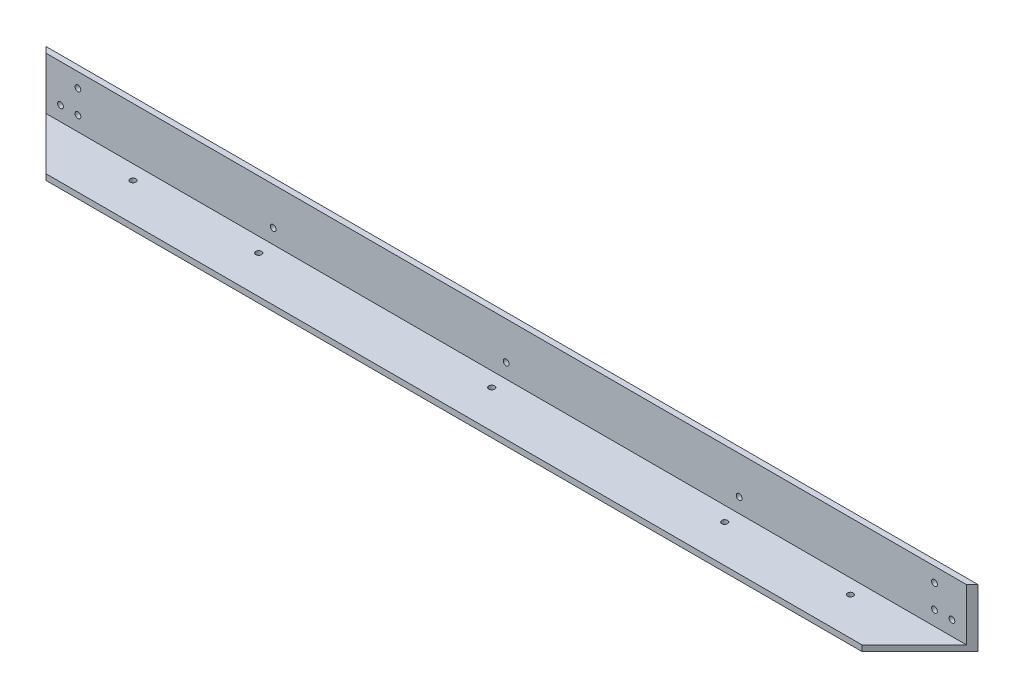
SolidWorks part; units mm, degrees
ref_plane "Front Plane" through (0, 0, 0) normal (0, 0, 1) x (1, 0, 0)
ref_plane "Top Plane" through (0, 0, 0) normal (0, 1, 0) x (1, 0, 0)
ref_plane "Right Plane" through (0, 0, 0) normal (1, 0, 0) x (0, 0, -1)
sketch "Sketch1" plane through (0, 0, 0) normal (1, 0, 0) x (0, 0, -1)
  line L0 (0, 0) -> (-31.75, 0)
  line L1 (-31.75, 0) -> (-31.75, 3.175)
  line L2 (-31.75, 3.175) -> (-3.175, 3.175)
  line L3 (-3.175, 3.175) -> (-3.175, 31.75)
  line L4 (-3.175, 31.75) -> (0, 31.75)
  line L5 (0, 31.75) -> (0, 0)
  dimension "LHeight" = 31.75
  dimension "LWidth" = 31.75
  dimension "LMaterialThickness" = 3.175
  dimension "D1" = 28.575
  dimension "D2" = 28.575
  dimension "D3" = 3.175
extrude "Boss-Extrude1" add sketch "Sketch1" along normal blind 510
chamfer "Chamfer6" distance 31.75 angle 45 1 edges at (510, 1.5875, 31.75)
chamfer "Chamfer7" distance 31.75 angle 45 1 edges at (0, 1.5875, 31.75)
sketch "TopHoles-Sketch3" plane through (0, 3.175, 0) normal (0, 1, 0) x (1, 0, 0)
  line L0 (510, 0) -> (0, 0) construction
  circle A9 centre (451.2625, -11.1125) radius 1.5875
  circle A10 centre (58.7375, -11.1125) radius 1.5875
  circle A13 centre (127.5, -11.1125) radius 1.5875
  circle A14 centre (255, -11.1125) radius 1.5875
  circle A15 centre (382.5, -11.1125) radius 1.5875
  point P8 (0, 0)
  point P9 (0, 0)
  point P10 (0, 0)
  point P11 (0, 0)
  point P12 (0, 0)
  point P13 (0, 0)
  point P14 (0, 0)
  dimension "D10" = 127.5
  dimension "D5" = 3.175
  dimension "D11" = 127.5
  dimension "D13" = 127.5
  dimension "D2" = 11.1125
  dimension "D3" = 58.7375
  dimension "D4" = 58.7375
extrude "TopHoles-Cut-Extrude2" cut sketch "TopHoles-Sketch3" against normal through all
sketch "FrontHoles-Sketch4" plane through (0, 0, 3.175) normal (0, 0, 1) x (1, 0, 0)
  line L0 (0, 0) -> (0, 31.75) construction
  line L1 (510, 0) -> (510, 31.75) construction
  line L3 (510, 31.75) -> (0, 31.75) construction
  line L7 (510, 0) -> (0, 0) construction
  circle A3 centre (489.3625, 23.8125) radius 1.5875
  circle A4 centre (20.6375, 23.8125) radius 1.5875
  circle A6 centre (11.1125, 11.1125) radius 1.5875
  circle A7 centre (20.6375, 11.1125) radius 1.5875
  circle A8 centre (489.3625, 11.1125) radius 1.5875
  circle A9 centre (498.8875, 11.1125) radius 1.5875
  circle A10 centre (127.5, 11.1125) radius 1.5875
  circle A11 centre (255, 11.1125) radius 1.5875
  circle A12 centre (382.5, 11.1125) radius 1.5875
  dimension "D2" = 3.175
  dimension "D7" = 11.1125
  dimension "D6" = 20.6375
  dimension "D5" = 20.6375
  dimension "D8" = 127.5
  dimension "D9" = 127.5
  dimension "D10" = 127.5
  dimension "D4" = 7.9375
  dimension "D11" = 11.1125
  dimension "D3" = 11.1125
extrude "FrontHoles-Cut-Extrude3" cut sketch "FrontHoles-Sketch4" against normal through all
equation "\"TopRailWidth\"= 1.25in"
equation "\"TopRailHeight\"= 1.25in"
equation "\"RailThickness\"= .125in'Spec"
equation "\"SideRailHoleY1FromEdge\"= \"HoleOffsetFromEdge\""
equation "\"SideRailHoleX1FromSide\"= \"HoleOffsetFromSide\""
equation "\"FrontBackRailLength\"= 510mm"
equation "\"VSWidth\"= 1.25in'Spec"
equation "\"HoleOffsetFromEdge\"= \"RailThickness\" * 2.5"
equation "\"HoleOffsetFromSide\"= \"RailThickness\" * 3.5"
equation "\"SideRailHoleX2FromSide\"= \"VSWidth\" - \"HoleOffsetFromEdge\" - \"RailThickness\"'Equals 20.6375"
equation "\"FasteningHoleDiameter\"= .125in"
equation "\"SideRailHoleY2FromSide\"= \"HoleOffsetFromSide\""
equation "\"LWidth@Sketch1\"=\"TopRailWidth\""
equation "\"LHeight@Sketch1\"=\"TopRailHeight\""
equation "\"LMaterialThickness@Sketch1\"=\"RailThickness\""
equation "\"D1@Boss-Extrude1\"= \"FrontBackRailLength\""
equation "\"D7@FrontHoles-Sketch4\"=\"SideRailHoleY2FromSide\""
equation "\"D1@Chamfer6\"=\"TopRailWidth\""
equation "\"D1@Chamfer7\"=\"TopRailWidth\""
equation "\"D6@FrontHoles-Sketch4\"=\"SideRailHoleX2FromSide\""
equation "\"TopHoleY1FromSide\"= \"HoleOffsetFromSide\""
equation "\"TopCBLength\"= \"TopRailWidth\" * 2'Equals 63.5"
equation "\"FrontOrBackEnclosureOffsets\"= \"FrontBackRailLength\" / 4"
equation "\"D10@TopHoles-Sketch3\"=\"FrontOrBackEnclosureOffsets\""
equation "\"D11@TopHoles-Sketch3\"=\"FrontOrBackEnclosureOffsets\""
equation "\"D13@TopHoles-Sketch3\"=\"FrontOrBackEnclosureOffsets\""
equation "\"D8@FrontHoles-Sketch4\"=\"FrontOrBackEnclosureOffsets\""
equation "\"D9@FrontHoles-Sketch4\"=\"FrontOrBackEnclosureOffsets\""
equation "\"D10@FrontHoles-Sketch4\"=\"FrontOrBackEnclosureOffsets\""
equation "\"D4@FrontHoles-Sketch4\"=\"SideRailHoleY1FromEdge\""
equation "\"D11@FrontHoles-Sketch4\"=\"SideRailHoleX1FromSide\""
equation "\"D2@FrontHoles-Sketch4\"=\"FasteningHoleDiameter\""
equation "\"D3@FrontHoles-Sketch4\"=\"SideRailHoleX1FromSide\""
equation "\"D5@FrontHoles-Sketch4\"=\"SideRailHoleX2FromSide\""
equation "\"D2@TopHoles-Sketch3\"=\"TopHoleY1FromSide\""
equation "\"D5@TopHoles-Sketch3\"=\"FasteningHoleDiameter\""
equation "\"FrontOrBackCornerEnclosureOffset\" = \"RailThickness\" + \"TopCBLength\" - \"HoleOffsetFromEdge\"'Equals 58.7375"
equation "\"D3@TopHoles-Sketch3\"=\"FrontOrBackCornerEnclosureOffset\""
